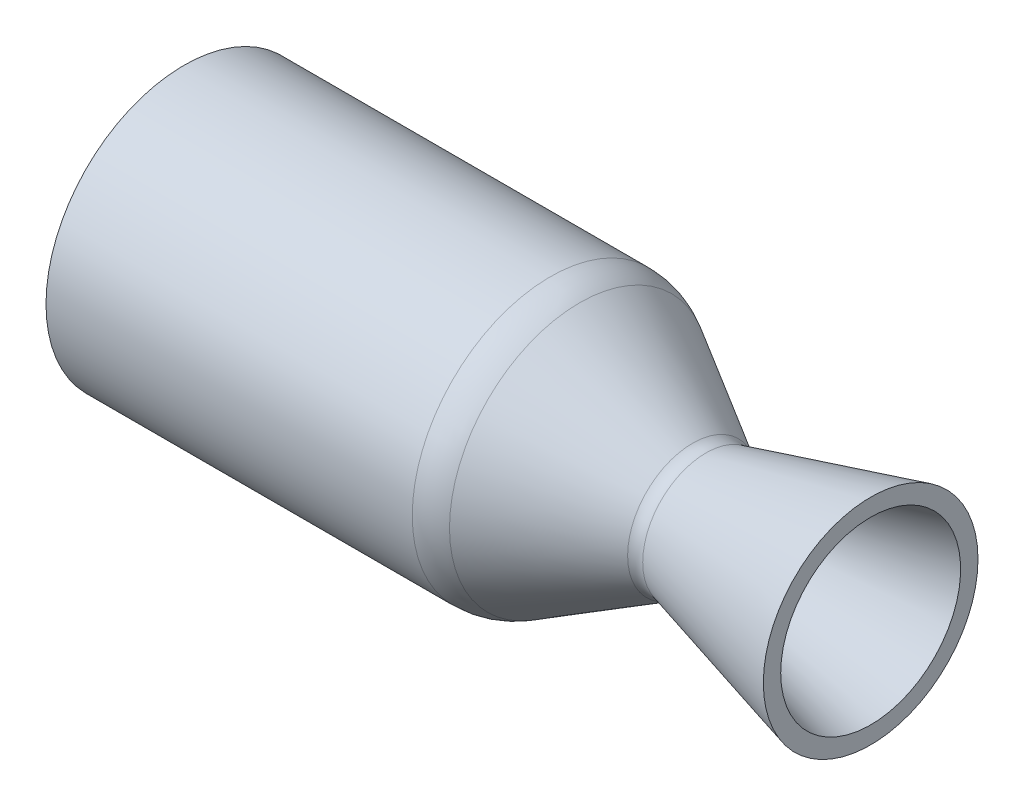
SolidWorks part; units mm, degrees
ref_plane "Front Plane" through (0, 0, 0) normal (0, 0, 1) x (1, 0, 0)
ref_plane "Top Plane" through (0, 0, 0) normal (0, 1, 0) x (1, 0, 0)
ref_plane "Right Plane" through (0, 0, 0) normal (1, 0, 0) x (0, 0, -1)
sketch "Sketch1" plane through (0, 0, 0) normal (0, 0, 1) x (1, 0, 0)
  line L0 (0, 0) -> (366.3783, 0) construction
  line L1 (0, 0) -> (0, 36.703) construction
  line L2 (0, 36.703) -> (110.897, 36.703)
  line L3 (156.6377, 24.2697) -> (156.6377, 13.8684) construction
  line L4 (117.247, 35.0015) -> (151.4371, 15.2619)
  line L5 (150.9294, 13.8684) -> (106.9103, 13.8684) construction
  line L6 (159.3298, 14.2228) -> (207.9067, 27.239)
  line L7 (207.9067, 27.239) -> (207.9067, 0) construction
  line L8 (0, 41.783) -> (110.897, 41.783)
  line L9 (119.787, 39.4009) -> (153.9771, 19.6613)
  line L10 (158.015, 19.1297) -> (207.9067, 32.4982)
  line L11 (0, 41.783) -> (0, 36.703)
  line L12 (207.9067, 27.239) -> (207.9067, 32.4982)
  line L13 (158.015, 19.1297) -> (206.5919, 32.1459) construction
  arc A0 (151.4371, 15.2619) -> (159.3298, 14.2228) centre (156.6377, 24.2697) ccw
  arc A1 (110.897, 36.703) -> (117.247, 35.0015) centre (110.897, 24.003) cw
  arc A2 (110.897, 41.783) -> (119.787, 39.4009) centre (110.897, 24.003) cw
  arc A3 (153.9771, 19.6613) -> (158.015, 19.1297) centre (156.6377, 24.2697) ccw
  point P16 (114.3, 36.703)
  dimension "D4" = 20.8026
  dimension "D9" = 12.7
  dimension "D1" = 36.703
  dimension "D2" = 114.3
  dimension "D3" = 13.8684
  dimension "D5" = 30
  dimension "D6" = 15
  dimension "D7" = 27.239
  dimension "D8" = 51.269
  dimension "D10" = 5.08
revolve "Revolve1" add sketch "Sketch1" angle 360 about L0
equation "\"D4@Sketch1\"=1.5*\"D3@Sketch1\""
